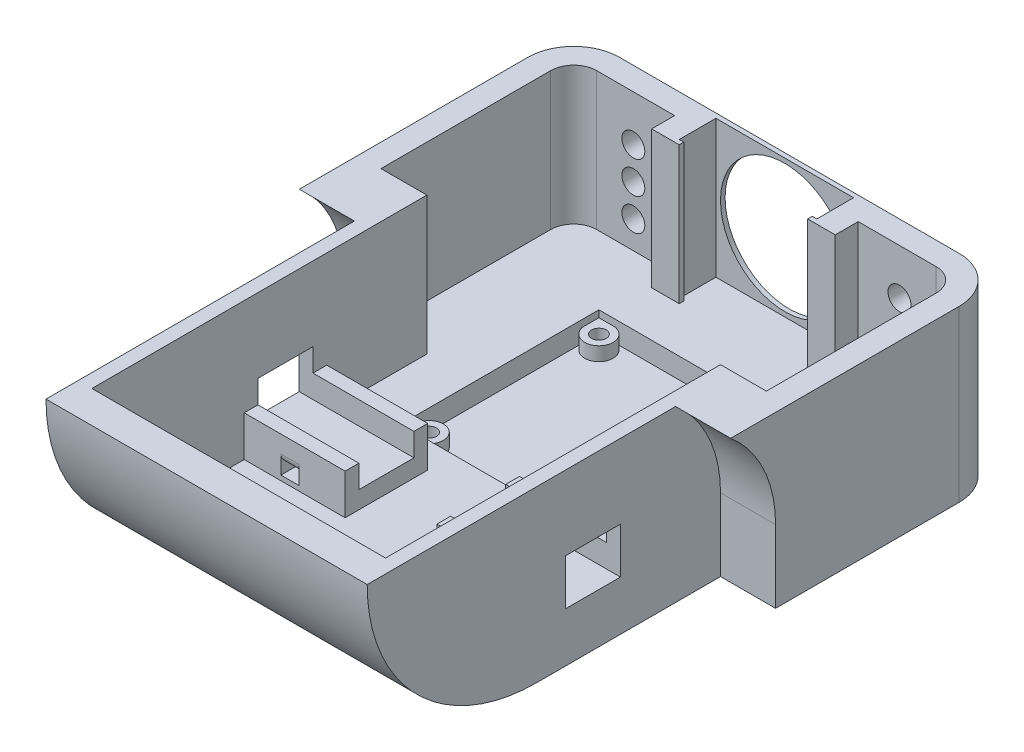
SolidWorks part; units mm, degrees
ref_plane "Front Plane" through (0, 0, 0) normal (0, 0, 1) x (1, 0, 0)
ref_plane "Top Plane" through (0, 0, 0) normal (0, 1, 0) x (1, 0, 0)
ref_plane "Right Plane" through (0, 0, 0) normal (1, 0, 0) x (0, 0, -1)
sketch "Sketch1" plane through (0, 0, 0) normal (0, 1, 0) x (1, 0, 0)
  line L0 (-18.5, 18.5) -> (-18.5, -18.5) construction
  line L1 (-18.5, -18.5) -> (18.5, -18.5) construction
  line L2 (18.5, -18.5) -> (18.5, 18.5) construction
  line L3 (18.5, 18.5) -> (-18.5, 18.5) construction
  line L4 (-21.5, 21.5) -> (-21.5, -21.5) construction
  line L5 (-21.5, -21.5) -> (21.5, -21.5) construction
  line L6 (21.5, -21.5) -> (21.5, 21.5) construction
  line L7 (-18.5, 18.5) -> (-21.5, 21.5) construction
  line L8 (-21.5, 21.5) -> (21.5, 21.5) construction
  line L9 (-18.5, -18.5) -> (-21.5, -21.5) construction
  line L10 (18.5, -18.5) -> (21.5, -21.5) construction
  line L11 (-18.5, 18.5) -> (0, 0) construction
  line L12 (0, 0) -> (18.5, -18.5) construction
  line L13 (-18.5, -18.5) -> (0, 0) construction
  line L14 (-35, -8.5) -> (-35, -48.5)
  line L15 (-35, -48.5) -> (35, -48.5)
  line L16 (35, -48.5) -> (35, -8.5)
  line L17 (35, -8.5) -> (47, -8.5)
  line L18 (47, -8.5) -> (47, 31.5)
  line L19 (-35, -8.5) -> (-47, -8.5)
  line L20 (-47, -8.5) -> (-47, 31.5)
  line L21 (-35, -8.5) -> (-21.5, 21.5) construction
  line L22 (21.5, 21.5) -> (35, -8.5) construction
  line L23 (-37, 41.5) -> (37, 41.5)
  line L24 (-21.6, -21.6) -> (21.6, -21.6)
  line L25 (21.6, -21.6) -> (21.6, 21.6)
  line L26 (-21.6, 21.6) -> (21.6, 21.6)
  line L27 (-21.6, 21.6) -> (-21.6, -21.6)
  line L28 (-21.5, -17.719) -> (-21.6, -17.719)
  line L29 (-17.719, -21.5) -> (-17.719, -21.6)
  line L30 (17.719, -21.5) -> (17.719, -21.6)
  line L31 (21.5, -17.719) -> (21.6, -17.719)
  line L32 (21.5, 17.719) -> (21.6, 17.719)
  line L33 (17.719, 21.5) -> (17.719, 21.6)
  line L34 (-21.5, 17.719) -> (-21.6, 17.719)
  line L35 (-17.719, 21.5) -> (-17.719, 21.6)
  circle A0 centre (-18.5, 18.5) radius 1.6
  circle A1 centre (18.5, 18.5) radius 1.6
  circle A2 centre (-18.5, -18.5) radius 1.6
  circle A3 centre (18.5, -18.5) radius 1.6
  arc A4 (-17.719, 21.5) -> (-21.5, 17.719) centre (-18.5, 18.5) cw
  arc A5 (-21.5, -17.719) -> (-17.719, -21.5) centre (-18.5, -18.5) cw
  arc A6 (17.719, -21.5) -> (21.5, -17.719) centre (18.5, -18.5) cw
  arc A7 (17.719, 21.5) -> (21.5, 17.719) centre (18.5, 18.5) ccw
  arc A8 (-47, 31.5) -> (-37, 41.5) centre (-37, 31.5) cw
  arc A9 (37, 41.5) -> (47, 31.5) centre (37, 31.5) cw
  dimension "D3" = 3.2
  dimension "D4" = 1.5
  dimension "D7" = 12
  dimension "D8" = 20
  dimension "D9" = 90
  dimension "D10" = 0.1
  dimension "D11" = 50
  dimension "D6" = 10
  dimension "D1" = 37
  dimension "D2" = 43
  dimension "D5" = 70
extrude "Boss-Extrude1" add sketch "Sketch1" against normal blind 7 contours L20 L19 L14 L15 L16 L17 L18 L4 L8 L6 L5 | A4 L8 L4 A0 | A0 | A7 L8 A4 L4 A5 L5 A6 L6 | A5 L4 L5 A2 | A2 | A6 L5 L6 A3 | A3 | L8 A7 L6 A1 | A1 region at (-41, 0, 7.1986) region at (-21.5123, 0, 19.6595) region at (0, 0, 0) region at (17.8067, 0, 21.55) region at (-21.5123, 0, -19.6595) region at (21.55, 0, -17.8067) region at (-18.5, 0, -18.5) region at (18.5, 0, -18.5) region at (-18.5, 0, 18.5) region at (18.5, 0, 18.5)
extrude "Cut-Extrude1" cut sketch "Sketch1<5>" against normal blind 1.5 contours A5 L4 L5 A2 | A2 | A7 L8 A4 L4 A5 L5 A6 L6 | A4 L8 L4 A0 | A0 | L8 A7 L6 A1 | A1 | A6 L5 L6 A3 | A3 region at (-21.5123, 0, 19.6595) region at (0, 0, 0) region at (17.8067, 0, 21.55) region at (-21.5123, 0, -19.6595) region at (21.55, 0, -17.8067) region at (-18.5, 0, -18.5) region at (18.5, 0, -18.5) region at (-18.5, 0, 18.5) region at (18.5, 0, 18.5)
sketch "Sketch1<5>" plane through (0, 0, 0) normal (0, 1, 0) x (1, 0, 0) same geometry as "Sketch1"
extrude "Cut-Extrude2" cut sketch "Sketch1<6>" against normal blind 3 from surface contours A7 L8 A4 L4 A5 L5 A6 L6 | A0 | A1 | A2 | A3 region at (0, 0, 0) region at (-18.5, 0, -18.5) region at (18.5, 0, -18.5) region at (-18.5, 0, 18.5) region at (18.5, 0, 18.5) starting at face at (0, -1.5, 0)
sketch "Sketch1<6>" plane through (0, 0, 0) normal (0, 1, 0) x (1, 0, 0) same geometry as "Sketch1"
sketch "Sketch3" plane through (0, 0, 0) normal (0, 1, 0) x (1, 0, 0)
  line L9 (47, -8.5) -> (47, 31.5) construction
  line L10 (-37, 41.5) -> (37, 41.5) construction
  line L11 (-47, -8.5) -> (-47, 31.5) construction
  line L18 (47, -8.5) -> (47, 31.5)
  line L19 (-37, 41.5) -> (37, 41.5)
  line L20 (-47, -8.5) -> (-47, 31.5)
  line L21 (-47, -8.5) -> (-42, -8.5)
  line L22 (42, -8.5) -> (47, -8.5)
  line L23 (-14, 41.5) -> (-14, 40.5)
  line L24 (-14, 40.5) -> (-15, 40.5)
  line L25 (-15, 40.5) -> (-15, 32.5)
  line L26 (-15, 32.5) -> (-14, 32.5)
  line L27 (-14, 32.5) -> (-14, 31.5)
  line L28 (14, 41.5) -> (14, 40.5)
  line L29 (14, 40.5) -> (15, 40.5)
  line L30 (15, 40.5) -> (15, 32.5)
  line L31 (15, 32.5) -> (14, 32.5)
  line L32 (14, 32.5) -> (14, 31.5)
  line L33 (-37, 31.5) -> (-15, 32.5) construction
  line L34 (15, 32.5) -> (37, 31.5) construction
  line L35 (-14, 31.5) -> (-20, 31.5)
  line L36 (-20, 31.5) -> (-20, 36.5)
  line L37 (-20, 36.5) -> (-37, 36.5)
  line L38 (-42, -8.5) -> (-42, 31.5)
  line L39 (-35, -8.5) -> (-47, -8.5) construction
  line L40 (14, 31.5) -> (20, 31.5)
  line L41 (20, 31.5) -> (20, 36.5)
  line L42 (20, 36.5) -> (37, 36.5)
  line L43 (42, -8.5) -> (42, 31.5)
  arc A6 (47, 31.5) -> (37, 41.5) centre (37, 31.5) ccw construction
  arc A7 (-37, 41.5) -> (-47, 31.5) centre (-37, 31.5) ccw construction
  arc A8 (47, 31.5) -> (37, 41.5) centre (37, 31.5) ccw
  arc A9 (-37, 41.5) -> (-47, 31.5) centre (-37, 31.5) ccw
  arc A10 (-42, 31.5) -> (-37, 36.5) centre (-37, 31.5) cw
  arc A11 (37, 36.5) -> (42, 31.5) centre (37, 31.5) cw
  arc M13 (47, 31.5) -> (37, 41.5) centre (37, 31.5) ccw
  line M14 (37, 41.5) -> (-37, 41.5)
  arc M15 (-37, 41.5) -> (-47, 31.5) centre (-37, 31.5) ccw
  line M16 (-47, 31.5) -> (-47, -8.5)
  line M17 (-47, -8.5) -> (-35, -8.5)
  line M21 (35, -8.5) -> (47, -8.5)
  line M22 (47, -8.5) -> (47, 31.5)
  dimension "D2" = 30
  dimension "D3" = 8
  dimension "D4" = 1
  dimension "D1" = 1
  dimension "D5" = 5
  dimension "D6" = 5
extrude "Boss-Extrude2" add sketch "Sketch3" along normal blind 30 contours L27 L26 L25 L24 L23 L19 M15 M16 M17 | L31 L32 L28 L29 L30 M21 M22 M13 M14 region at (44.5, 0, 7.9009) region at (-14.5991, 0, -41)
sketch "Sketch5" plane through (0, 0, 0) normal (1, 0, 0) x (0, 0, -1)
  line L0 (-48.5, 0) -> (-48.5, -7)
  line L1 (-78.5, 30) -> (-85.5, 30)
  line L2 (31.5, 30) -> (-8.5, 30) construction
  line L3 (-48.5, 0) -> (-43.4308, 0) construction
  line L4 (-8.5, 0) -> (-48.5, 0) construction
  line L5 (-78.5, 30) -> (-78.5, 34.1499) construction
  arc A0 (-48.5, 0) -> (-78.5, 30) centre (-48.5, 30) cw
  arc A1 (-48.5, -7) -> (-85.5, 30) centre (-48.5, 30) cw
extrude "Boss-Extrude3" add sketch "Sketch5" against normal up to surface and the other way up to surface up to face at (-35, -3.5, 28.5) other way up to face at (35, -3.5, 28.5)
ref_plane "Plane1" through (0, -24.25, 24.25) normal (0, -0.7071, 0.7071) x (-1, 0, 0)
sketch "Sketch6" plane through (0, -24.25, 24.25) normal (0, -0.7071, 0.7071) x (-1, 0, 0)
  line L0 (-21.59, -65.9179) -> (-14.99, -63.4179) construction
  line L1 (-21.59, -65.9179) -> (21.59, -65.9179) construction
  line L2 (-21.59, -65.9179) -> (-21.59, -45.0979) construction
  line L3 (-21.59, -45.0979) -> (21.59, -45.0979) construction
  line L4 (21.59, -65.9179) -> (21.59, -45.0979) construction
  line L5 (-35, -34.2947) -> (-21.59, -45.0979) construction
  line L6 (14.99, -47.5979) -> (21.59, -45.0979) construction
  line L7 (-21.59, -45.0979) -> (14.99, -47.5979) construction
  line L8 (-14.99, -63.4179) -> (21.59, -65.9179) construction
  line L9 (-35, -76.7211) -> (-21.59, -65.9179) construction
  line L10 (21.59, -65.9179) -> (35, -76.7211) construction
  line L11 (-21.59, -64.4179) -> (21.59, -64.4179)
  line L12 (-21.59, -46.5979) -> (21.59, -46.5979)
  line L13 (-21.69, -66.0179) -> (-21.69, -44.9979)
  line L14 (-21.69, -44.9979) -> (21.69, -44.9979)
  line L15 (21.69, -66.0179) -> (21.69, -44.9979)
  line L16 (-21.69, -66.0179) -> (21.69, -66.0179)
  line L17 (-21.59, -64.4179) -> (-21.69, -64.4179)
  line L18 (-21.59, -46.5979) -> (-21.69, -46.5979)
  line L19 (21.59, -46.5979) -> (21.69, -46.5979)
  line L20 (21.59, -64.4179) -> (21.69, -64.4179)
  circle A0 centre (-14.99, -63.4179) radius 1.5
  circle A1 centre (14.99, -47.5979) radius 1.5
  arc A2 (-17.8184, -64.4179) -> (-12.1616, -64.4179) centre (-14.99, -63.4179) cw
  arc A3 (17.8184, -46.5979) -> (12.1616, -46.5979) centre (14.99, -47.5979) cw
  dimension "D5" = 3
  dimension "D8" = 1.5
  dimension "D1" = 43.18
  dimension "D2" = 20.82
  dimension "D3" = 6.6
  dimension "D4" = 2.5
  dimension "D6" = 1.5
  dimension "D7" = 1.5
  dimension "D9" = 0.1
extrude "Cut-Extrude3" cut sketch "Sketch6" along normal blind 9 contours A1 L12 L4 L3 L2 | L12 A1 | L12 A1 | A3 L12 A1 | L12 A3 L2 L11 A2 L4 | A2 L11 A0 | L11 A0 | A0 L11 L2 L1 L4 | L11 A0 region at (0, 15, 63.5) region at (-0.1691, 21.8708, 70.3708) region at (14.99, 18.5229, 67.0229) region at (14.99, 20.4885, 68.9885) region at (14.99, 21.444, 69.944) region at (0.1691, 8.1292, 56.6292) region at (-13.0168, 8.7507, 57.2507) region at (-14.99, 8.556, 57.056) region at (-14.99, 9.5115, 58.0115)
extrude "Cut-Extrude4" cut sketch "Sketch6<3>" along normal blind 3 from surface contours L12 A1 | L12 A1 | L12 A3 L2 L11 A2 L4 | L11 A0 | L11 A0 region at (0, 15, 63.5) region at (14.99, 20.4885, 68.9885) region at (14.99, 21.444, 69.944) region at (-14.99, 8.556, 57.056) region at (-14.99, 9.5115, 58.0115) starting at face at (0, 8.636, 69.864)
sketch "Sketch6<3>" plane through (0, -24.25, 24.25) normal (0, -0.7071, 0.7071) x (-1, 0, 0) same geometry as "Sketch6"
sketch "Sketch7" plane through (0, 0, 0) normal (0, 1, 0) x (1, 0, 0)
  line L0 (35, -8.5) -> (42, -8.5) construction
  line L1 (35, -48.5) -> (35, -8.5) construction
  line L2 (-35, -8.5) -> (-35, -48.5) construction
  line L3 (-35, -8.5) -> (-42, -8.5) construction
  line L4 (35, -8.5) -> (42, -8.5)
  line L5 (35, -48.5) -> (35, -8.5)
  line L6 (-35, -8.5) -> (-35, -48.5)
  line L7 (-35, -8.5) -> (-42, -8.5)
  line L8 (32, -48.5) -> (32, -5.5)
  line L9 (32, -5.5) -> (42, -5.5)
  line L10 (-32, -5.5) -> (-42, -5.5)
  line L11 (-32, -5.5) -> (-32, -48.5)
  line L12 (42, -5.5) -> (42, -8.5)
  line L13 (35, -48.5) -> (32, -48.5)
  line L14 (-32, -48.5) -> (-35, -48.5)
  line L15 (-42, -5.5) -> (-42, -8.5)
  line M9 (35, -8.5) -> (42, -8.5)
  line M25 (-42, -8.5) -> (-35, -8.5)
  line M26 (-35, -8.5) -> (-35, -48.5)
  line M27 (-35, -48.5) -> (35, -48.5)
  line M28 (35, -48.5) -> (35, -8.5)
  dimension "D1" = 3
extrude "Boss-Extrude4" add sketch "Sketch7" along normal up to surface (30 mm away) contours L11 L10 M25 M26 M27 | L9 L8 M27 M28 M9 region at (34.2, 0, 24.2) region at (-34.2, 0, 24.2) up to face at (-27.2219, 30, -29.579)
sketch "Sketch8" plane through (0, 0, 48.5) normal (0, 0, 1) x (1, 0, 0)
  line L0 (35, 30) -> (32, 30) construction
  line L1 (32, 30) -> (32, 0) construction
  line L2 (32, 0) -> (35, 0) construction
  line L3 (35, 0) -> (35, 30) construction
  line L4 (-32, 30) -> (-35, 30) construction
  line L5 (-35, 30) -> (-35, 0) construction
  line L6 (-35, 0) -> (-32, 0) construction
  line L7 (-32, 0) -> (-32, 30) construction
  line L8 (35, 30) -> (32, 30)
  line L9 (32, 30) -> (32, 0)
  line L10 (32, 0) -> (35, 0)
  line L11 (35, 0) -> (35, 30)
  line L12 (-32, 30) -> (-35, 30)
  line L13 (-35, 30) -> (-35, 0)
  line L14 (-35, 0) -> (-32, 0)
  line L15 (-32, 0) -> (-32, 30)
extrude "Boss-Extrude6" add sketch "Sketch8" along normal up to surface up to face at (0, 9.459, 69.041)
sketch "Sketch9" plane through (0, 0, -41.5) normal (0, 0, -1) x (-1, 0, 0)
  line L0 (-29, 6) -> (-29, 13) construction
  line L1 (-29, 13) -> (-29, 20) construction
  line L2 (29, 20) -> (29, 13) construction
  line L3 (29, 13) -> (29, 6) construction
  line L4 (-37, 30) -> (-29, 20) construction
  line L5 (-29, 20) -> (-14, 30) construction
  line L6 (14, 30) -> (29, 20) construction
  line L7 (29, 20) -> (37, 30) construction
  line L8 (-14, 30) -> (-14, 0) construction
  line L9 (-37, 30) -> (-14, 30) construction
  circle A0 centre (-29, 20) radius 2.5
  circle A1 centre (-29, 13) radius 2.5
  circle A2 centre (-29, 6) radius 2.5
  circle A3 centre (29, 20) radius 2.5
  circle A4 centre (29, 13) radius 2.5
  circle A5 centre (29, 6) radius 2.5
  dimension "D1" = 5
  dimension "D2" = 7
  dimension "D3" = 15
  dimension "D4" = 10
extrude "Cut-Extrude5" cut sketch "Sketch9" against normal up to surface (5 mm away) contours A0 | A1 | A2 | A3 | A4 | A5 region at (29, 20, -41.5) region at (29, 13, -41.5) region at (29, 6, -41.5) region at (-29, 20, -41.5) region at (-29, 13, -41.5) region at (-29, 6, -41.5) up to face at (-28.5, 15, -36.5)
sketch "Sketch10" plane through (0, 0, 0) normal (1, 0, 0) x (0, 0, -1)
  line L0 (-30.3125, 13.8125) -> (-30.3125, 3.8125)
  line L1 (-8.5, 30) -> (-85.5, 30) construction
  line L2 (-42.3125, 13.8125) -> (-42.3125, 3.8125)
  line L3 (-36.3125, 8.8125) -> (-36.3125, -15) construction
  line L4 (-36.3125, 8.8125) -> (-12.5, 8.8125) construction
  line L5 (-8.5, -7) -> (-48.5, -7) construction
  line L6 (-8.5, -7) -> (-8.5, 30) construction
  line L7 (-30.3125, 13.8125) -> (-42.3125, 13.8125)
  line L8 (-30.3125, 3.8125) -> (-42.3125, 3.8125)
  line L9 (-30.3125, 3.8125) -> (-36.3125, 8.8125) construction
  line L10 (-36.3125, 8.8125) -> (-42.3125, 13.8125) construction
  line L11 (-36.3125, 8.8125) -> (-42.3125, 3.8125) construction
  line L12 (-27.3125, 0) -> (-45.3125, 0)
  line L13 (-27.3125, 0) -> (-27.3125, 8.8125)
  line L14 (-27.3125, 8.8125) -> (-30.3125, 8.8125)
  line L15 (-42.3125, 8.8125) -> (-45.3125, 8.8125)
  line L16 (-45.3125, 8.8125) -> (-45.3125, 0)
  line L17 (-5.5, 0) -> (31.5, 0) construction
  line L18 (-8.5, 8.8125) -> (-8.5, 30)
  line L19 (-8.5, -7) -> (-8.5, 30) construction
  line L20 (-8.5, 30) -> (-18.2951, 30)
  line L21 (-8.5, 30) -> (-85.5, 30) construction
  line L23 (-48.5, -7) -> (-8.5, -7) construction
  line L24 (41.5, -7) -> (41.5, 30) construction
  circle A1 centre (-36.3125, 8.8125) radius 23.8125 construction
  arc A2 (-8.5, 8.8125) -> (-18.2951, 30) centre (-36.3125, 8.8125) ccw
  dimension "D1" = 47.625
  dimension "D4" = 12
  dimension "D2" = 8
  dimension "D3" = 4
  dimension "D5" = 5
  dimension "D6" = 3
  dimension "D7" = 5
  dimension "D8" = 10
  dimension "D9" = 21.1875
  dimension "D10" = 37
  dimension "D11" = 77.8125
extrude "Cut-Extrude6" cut sketch "Sketch10" against normal through all both and the other way through all contours L8 L0 L7 L2 region at (0, 8.8125, 36.3125)
extrude "Boss-Extrude7" add sketch "Sketch10<3>" along normal up to surface (32 mm away) from offset 10 contours L15 L16 L12 L13 L14 L0 L8 L2 region at (0, 3.2466, 36.3125) up to face at (32, 13.4467, 36.0533)
sketch "Sketch10<3>" plane through (0, 0, 0) normal (1, 0, 0) x (0, 0, -1) same geometry as "Sketch10"
extrude "Boss-Extrude8" add sketch "Sketch10<4>" against normal up to surface (32 mm away) from offset 10 contours L15 L16 L12 L13 L14 L0 L8 L2 region at (0, 3.2466, 36.3125) up to face at (-32, 13.4467, 36.0533) offset against normal yes
sketch "Sketch10<4>" plane through (0, 0, 0) normal (1, 0, 0) x (0, 0, -1) same geometry as "Sketch10"
extrude "Boss-Extrude9" add sketch "Sketch10<5>" against normal up to surface (47 mm away) from surface contours A2 L18 L20 region at (0, 24.9078, 11.3221) up to face at (-47, 11.5, -11.5) starting at face at (-35, 9.5843, 39.6657)
sketch "Sketch10<5>" plane through (0, 0, 0) normal (1, 0, 0) x (0, 0, -1) same geometry as "Sketch10"
extrude "Boss-Extrude10" add sketch "Sketch10<6>" along normal up to surface (47 mm away) from surface contours A2 L18 L20 region at (0, 24.9078, 11.3221) up to face at (47, 11.5, -11.5) starting at face at (35, 9.5843, 39.6657)
sketch "Sketch10<6>" plane through (0, 0, 0) normal (1, 0, 0) x (0, 0, -1) same geometry as "Sketch10"
sketch "Sketch12" plane through (0, -7, 0) normal (0, -1, 0) x (1, 0, 0)
  line L0 (-22.5, -16.5) -> (22.5, -16.5) construction
  line L1 (-13.5, -11.3038) -> (-22.5, -6.1077)
  line L2 (-22.5, -6.1077) -> (-31.5, -11.3038)
  line L3 (-31.5, -11.3038) -> (-31.5, -21.6962)
  line L4 (-31.5, -21.6962) -> (-22.5, -26.8923)
  line L5 (-22.5, -26.8923) -> (-13.5, -21.6962)
  line L6 (-13.5, -21.6962) -> (-13.5, -11.3038)
  line L7 (31.5, -11.3038) -> (22.5, -6.1077)
  line L8 (22.5, -6.1077) -> (13.5, -11.3038)
  line L9 (13.5, -11.3038) -> (13.5, -21.6962)
  line L10 (13.5, -21.6962) -> (22.5, -26.8923)
  line L11 (22.5, -26.8923) -> (31.5, -21.6962)
  line L12 (31.5, -21.6962) -> (31.5, -11.3038)
  line L13 (22.5, -16.5) -> (0, 0) construction
  line L14 (0, 0) -> (-22.5, -16.5) construction
  line L15 (-37, -41.5) -> (37, -41.5) construction
  circle A0 centre (-22.5, -16.5) radius 9 construction
  circle A1 centre (22.5, -16.5) radius 9 construction
  dimension "D1" = 18
  dimension "D2" = 45
  dimension "D3" = 25
extrude "Boss-Extrude11" add sketch "Sketch12" along normal blind 5
chamfer "Chamfer1" distance 5 angle 45 12 edges at (27, -7, -8.7058) (18, -7, -8.7058) (13.5, -7, -16.5) (18, -7, -24.2942) (27, -7, -24.2942) (31.5, -7, -16.5) (-18, -7, -8.7058) (-27, -7, -8.7058) (-31.5, -7, -16.5) (-27, -7, -24.2942) (-18, -7, -24.2942) (-13.5, -7, -16.5)
sketch "Sketch13" plane through (0, 0, -41.5) normal (0, 0, -1) x (-1, 0, 0)
  line L0 (-14, 30) -> (-14, 0) construction
  line L1 (14, 30) -> (14, 0) construction
  line L4 (-14, 0) -> (0, 15) construction
  line L5 (0, 15) -> (-14, 30) construction
  line L6 (-14, 30) -> (14, 30)
  line L7 (14, 30) -> (14, 0)
  line L8 (14, 0) -> (-14, 0)
  line L9 (-14, 0) -> (-14, 30)
  circle A0 centre (0, 15) radius 14
  line M10 (14, 30) -> (14, 0)
  line M11 (14, 0) -> (-14, 0)
  line M12 (-14, 0) -> (-14, 30)
extrude "Boss-Extrude12" add sketch "Sketch13" against normal up to surface (1 mm away) contours A0 L6 L9 M10 | A0 L7 M12 M11 region at (0, 29.6824, -41.5) region at (0, 0.6824, -41.5) up to face at (14.5, 15, -40.5)
sketch "Sketch14" plane through (0, 0, 27.3125) normal (0, 0, -1) x (-1, 0, 0)
  line L0 (-10, 3.8125) -> (-35, 3.8125) construction
  line L1 (-24, 3.0625) -> (-20, 3.0625)
  line L2 (-24, 3.0625) -> (-24, 1.0625)
  line L3 (-24, 1.0625) -> (-20, 1.0625)
  line L4 (-20, 3.0625) -> (-20, 1.0625)
  line L5 (-10, 0) -> (-10, 8.8125) construction
  dimension "D1" = 2
  dimension "D2" = 4
  dimension "D3" = 0.75
  dimension "D4" = 10
extrude "Cut-Extrude7" cut sketch "Sketch14" against normal up to surface (18 mm away) up to face at (21, 4.4062, 45.3125)
mirror "Mirror2" about plane through (0, 0, 0) normal (1, 0, 0) of "Cut-Extrude7"
fillet "Fillet1" radius 2 4 edges at (22, 3.0625, 45.3125) (22, 3.0625, 27.3125) (-22, 3.0625, 45.3125) (-22, 3.0625, 27.3125)
